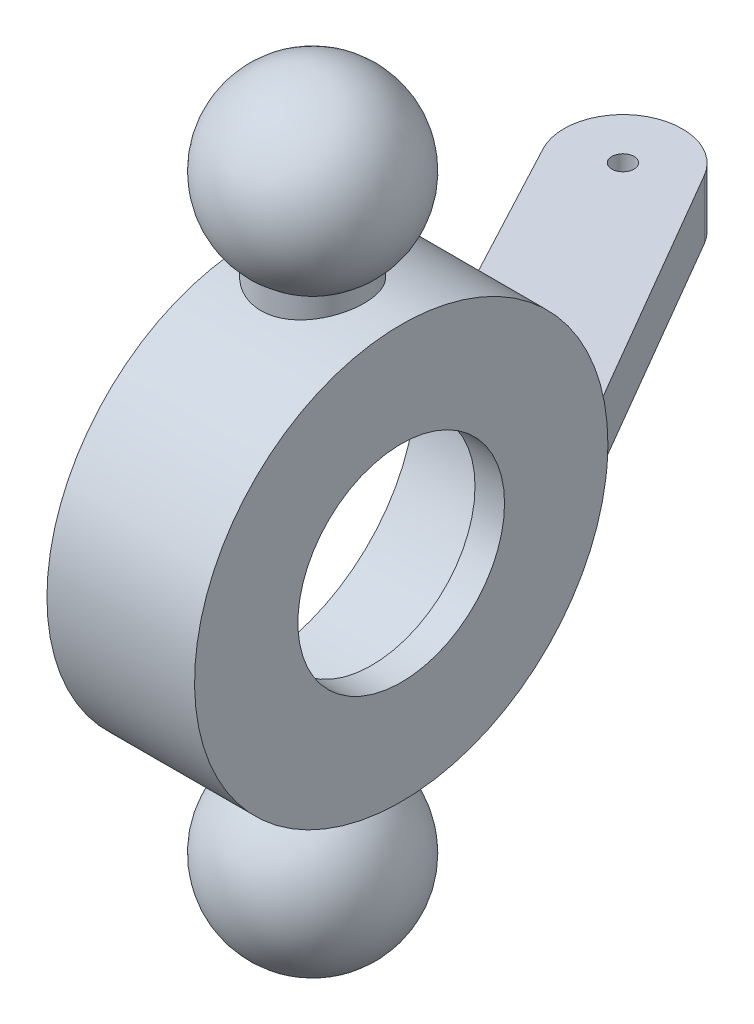
SolidWorks part; units mm, degrees
ref_plane "Front Plane" through (0, 0, 0) normal (0, 0, 1) x (1, 0, 0)
ref_plane "Top Plane" through (0, 0, 0) normal (0, 1, 0) x (1, 0, 0)
ref_plane "Right Plane" through (0, 0, 0) normal (1, 0, 0) x (0, 0, -1)
sketch "Sketch1" plane through (0, 0, 0) normal (1, 0, 0) x (0, 0, -1)
  circle A0 centre (0, 0) radius 11
  circle A1 centre (0, 0) radius 14
  dimension "D1" = 22
  dimension "D2" = 3
extrude "Boss-Extrude1" add sketch "Sketch1" along normal blind 8
ref_plane "Plane1" through (4, 0, 0) normal (1, 0, 0) x (0, 0, -1)
sketch "Sketch2" plane through (4, 0, 0) normal (1, 0, 0) x (0, 0, -1)
  line L0 (0, 12) -> (0, 20) construction
  line L2 (0, 12) -> (3.5, 12)
  line L3 (0, 12) -> (0, 20)
  line L4 (0, 20) -> (3.5, 20)
  line L5 (3.5, 12) -> (3.5, 20)
  circle A0 centre (0, 0) radius 11 construction
  dimension "D1" = 3.5
  dimension "D2" = 12
  dimension "D3" = 8
revolve "Revolve1" add sketch "Sketch2" angle 360 about L0
sketch "Sketch3" plane through (4, 0, 0) normal (1, 0, 0) x (0, 0, -1)
  line L0 (3.5, 20) -> (-3.5, 20) construction
  line L1 (0, 14) -> (0, 26)
  arc A0 (0, 14) -> (0, 26) centre (0, 20) ccw
  dimension "D1" = 6
revolve "Revolve2" add sketch "Sketch3" angle 360 about L1 region at (4, 20, -2.5465)
mirror "Mirror1" about plane through (0, 0, 0) normal (0, 1, 0) of "Revolve2", "Revolve1"
sketch "Sketch4" plane through (8, 0, 0) normal (1, 0, 0) x (0, 0, -1)
  circle A0 centre (0, 0) radius 14
  circle A1 centre (0, 0) radius 7
  dimension "D1" = 14
  dimension "D2" = 28
extrude "Boss-Extrude2" add sketch "Sketch4" along normal blind 2
sketch "Sketch5" plane through (0, 0, 0) normal (0, 1, 0) x (1, 0, 0)
  line L0 (10, -14) -> (10, 14) construction
  line L1 (10, 13) -> (0, 13)
  line L5 (10, 14) -> (0, 14) construction
  line L11 (10, 13) -> (-0.4773, 31.0113)
  line L12 (-3.9349, 33) -> (-3.9771, 33)
  line L13 (-7.5089, 27.1221) -> (0, 13)
  line L14 (0, 14) -> (0, -14) construction
  line L15 (5, 13) -> (-5.9343, 32.4884) construction
  arc A3 (-3.9771, 33) -> (-7.5089, 27.1221) centre (-3.9771, 29) ccw
  arc A4 (-0.4773, 31.0113) -> (-3.9349, 33) centre (-3.9349, 29) ccw
  circle A5 centre (-3.9771, 29) radius 0.75
  point P13 (-10.6342, 33)
  point P16 (-1.6342, 33)
  dimension "D5" = 0
  dimension "D6" = 4
  dimension "D3" = 20
  dimension "D7" = 1.5
  dimension "D1" = 1
  dimension "D2" = 9
  dimension "D4" = 152
extrude "Boss-Extrude3" add sketch "Sketch5" along normal blind 2 and the other way blind 2
